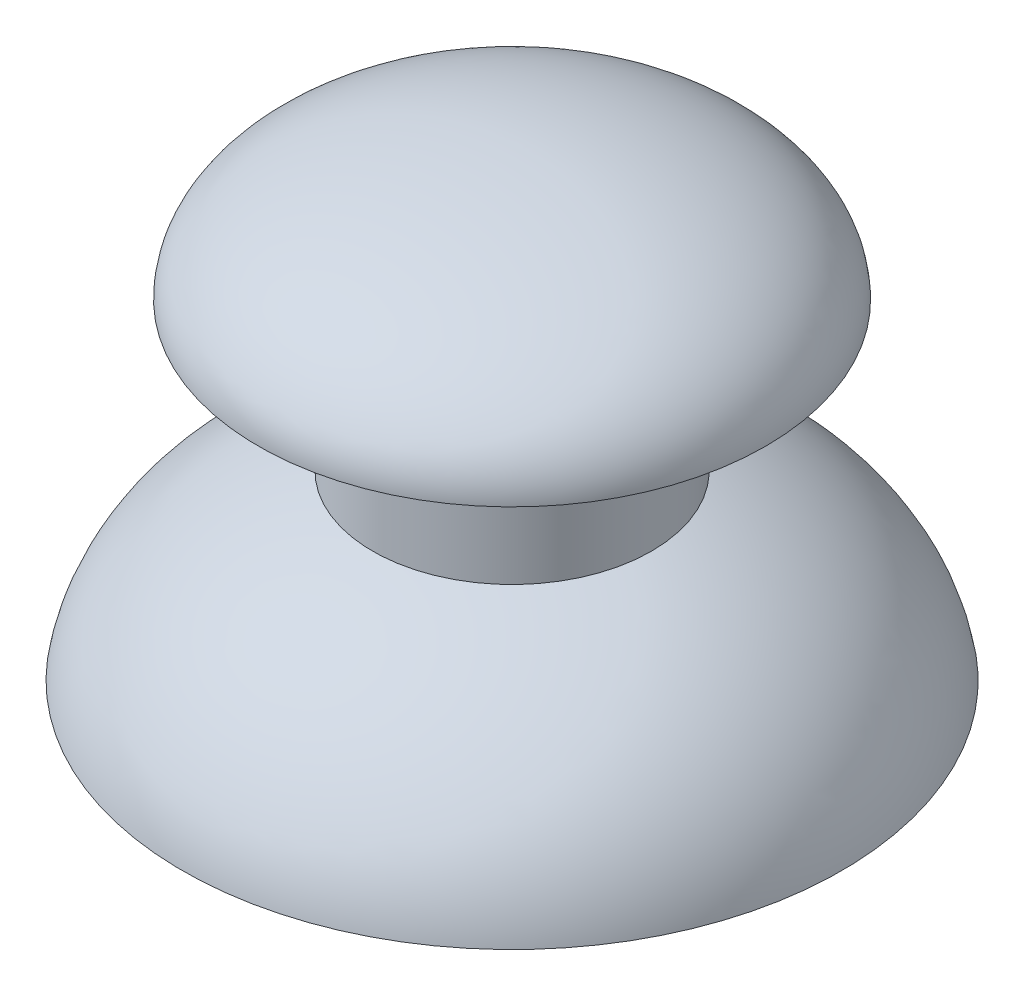
SolidWorks part; units mm, degrees
ref_plane "前视基准面" through (0, 0, 0) normal (0, 0, 1) x (1, 0, 0)
ref_plane "上视基准面" through (0, 0, 0) normal (0, 1, 0) x (1, 0, 0)
ref_plane "右视基准面" through (0, 0, 0) normal (1, 0, 0) x (0, 0, -1)
other "Configuration Table"
sketch "草图1" plane through (0, 0, 0) normal (0, 0, 1) x (1, 0, 0)
  line L1 (-13, 9) -> (0, 9)
  line L2 (-13, 9) -> (-13, -9)
  line L3 (-13, -9) -> (0, -9)
  line L4 (0, 9) -> (0, -9)
  line L9 (0, 4) -> (-5.5, 4)
  line L10 (0, 4) -> (0, -2)
  line L11 (0, -2) -> (-5.5, -2)
  line L12 (-5.5, 4) -> (-5.5, -2)
  line L13 (-13, -2) -> (0, -2)
  line L14 (-13, -2) -> (-13, -9)
  line L15 (-13, -9) -> (0, -9)
  line L16 (0, -2) -> (0, -9)
  line L17 (0, 9) -> (-10, 9)
  line L18 (0, 9) -> (0, 4)
  line L19 (0, 4) -> (-10, 4)
  line L20 (-10, 9) -> (-10, 4)
  ellipse E0 centre (0, 4) end of major axis (-10, 4) minor radius 5
  ellipse E1 centre (0, -10) end of major axis (-13.081, -10) minor radius 9
  ellipse E2 centre (0, -10) end of major axis (-12.081, -10) minor radius 8
  point P4 (0, 0)
  dimension "D1" = 13
  dimension "D2" = 18
  dimension "D3" = 5
  dimension "D4" = 5.5
  dimension "D5" = 6
  dimension "D6" = 10
  dimension "D7" = 1
  dimension "D8" = 1
  dimension "D9" = 1
sketch "草图3" plane through (0, 0, 0) normal (0, 0, 1) x (1, 0, 0)
  line L0 (-5.5, 4) -> (-5.5, -2) construction
  line L1 (0, 9) -> (0, -9) construction
  line L2 (-5.5, 4) -> (-5.5, -1.8342)
  line L3 (0, 9) -> (0, -9)
  line L4 (-13, -9) -> (0, -9) construction
  line L5 (-13, -9) -> (0, -9)
  line L6 (0, 4) -> (-10, 4) construction
  line L7 (-5.5, 4) -> (-10, 4)
  ellipse E0 centre (0, -10) end of major axis (-13.081, -10) minor radius 9 construction
  ellipse E1 centre (0, 4) end of major axis (-10, 4) minor radius 5 construction
  ellipse E2 centre (0, -10) end of major axis (-13.081, -10) minor radius 9 (-5.5, -1.8342) -> (-13, -9) ccw
  ellipse E3 centre (0, 4) end of major axis (-10, 4) minor radius 5 (0, 9) -> (-10, 4) ccw
revolve "旋转1" add sketch "草图3" angle 360 about L3
sketch "草图4" plane through (0, 0, 0) normal (0, 0, 1) x (1, 0, 0)
  line L0 (-13, -9) -> (0, -9) construction
  line L1 (0, 9) -> (0, -9) construction
  line L2 (-11.9862, -9) -> (0, -9)
  line L3 (0, 9) -> (0, -9)
  ellipse E0 centre (0, -10) end of major axis (-12.081, -10) minor radius 8 construction
  ellipse E1 centre (0, -10) end of major axis (-12.081, -10) minor radius 8 (0, -2) -> (-11.9862, -9) ccw
revolve "切除-旋转7" cut sketch "草图4" angle 360 about L3 region at (-4.958, -6.0582, 0)
sketch "草图5" plane through (0, 0, 0) normal (0, 1, 0) x (1, 0, 0)
  circle A0 centre (0, 0) radius 3
  circle A1 centre (0, 0) radius 4.5
  dimension "D1" = 6
  dimension "D2" = 9
extrude "凸台-拉伸1" add sketch "草图5" along direction (0, -1, 0) on the side against the normal offset from surface (6 mm away) 3 contours A0 up to face at (-11.9862, -9, 0)
extrude "切除-拉伸3" cut sketch "草图5<3>" along normal offset from surface (15 mm away) 6 from surface contours A0 | A1 up to plane "上视基准面" offset beyond the face yes starting at face at (-11.9862, -9, 0)
sketch "草图5<3>" plane through (0, 0, 0) normal (0, 1, 0) x (1, 0, 0) same geometry as "草图5"
sketch "草图6" plane through (0, 0, 0) normal (0, 0, 1) x (1, 0, 0)
  line L0 (0, 9) -> (0, -9) construction
  line L1 (0, 9) -> (0, -9)
  line L3 (-3, -6) -> (3, -6) construction
  line L4 (-3, -6) -> (3, -6)
  line L6 (-2.9, -5) -> (-9.5833, -5)
  line L7 (-2.9, -5) -> (-2.9, -2.1329)
  line L8 (-3, -2.2506) -> (-3, -5)
  ellipse E0 centre (0, -10) end of major axis (-12.081, -10) minor radius 8 construction
  ellipse E1 centre (0, -10) end of major axis (-12.081, -10) minor radius 8
  ellipse E2 centre (0, -10) end of major axis (-12.181, -10) minor radius 8.1
  dimension "D1" = 1
  dimension "D2" = 0.1
  dimension "D3" = 0.1
  dimension "D4" = 0.1
sketch "草图9" plane through (0, 0, 0) normal (0, 0, 1) x (1, 0, 0)
  line L0 (-2.9, -5) -> (-2.9, -2.1329) construction
  line L1 (-2.9, -5) -> (-9.5833, -5) construction
  line L2 (-2.9, -5) -> (-2.9, -2.1329)
  line L3 (-2.9, -5) -> (-9.5833, -5)
  ellipse E0 centre (0, -10) end of major axis (-12.181, -10) minor radius 8.1 construction
  ellipse E1 centre (0, -10) end of major axis (-12.181, -10) minor radius 8.1 (-2.9, -2.1329) -> (-9.5833, -5) ccw
extrude "凸台-拉伸5" add sketch "草图9" along normal mid plane 1
pattern_circular "阵列(圆周)1" count 4 over 360 of "凸台-拉伸5"
sketch "草图10" plane through (0, -6, 0) normal (0, -1, 0) x (1, 0, 0)
  line L1 (-1.05, -0.6) -> (1.05, -0.6)
  line L2 (-1.05, -0.6) -> (-1.05, 0.6)
  line L3 (-1.05, 0.6) -> (1.05, 0.6)
  line L4 (1.05, -0.6) -> (1.05, 0.6)
  line L5 (-1.05, -0.6) -> (1.05, 0.6) construction
  line L6 (-1.05, 0.6) -> (1.05, -0.6) construction
  point P0 (0, 0)
  dimension "D1" = 2.1
  dimension "D2" = 1.2
extrude "切除-拉伸4" cut sketch "草图10" against normal blind 4
